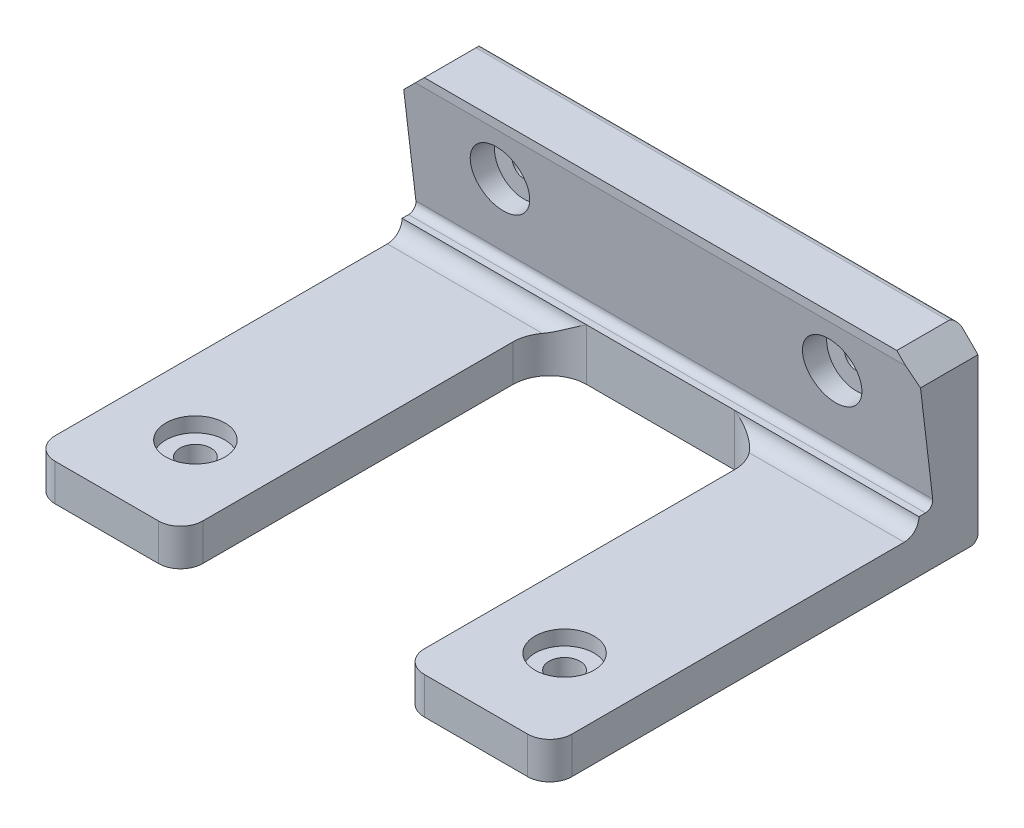
SolidWorks part; units mm, degrees
ref_plane "Přední rovina" through (0, 0, 0) normal (0, 0, 1) x (1, 0, 0)
ref_plane "Horní rovina" through (0, 0, 0) normal (0, 1, 0) x (1, 0, 0)
ref_plane "Pravá rovina" through (0, 0, 0) normal (1, 0, 0) x (0, 0, -1)
sketch "Sketch1" plane through (0, 0, 0) normal (0, 0, 1) x (1, 0, 0)
  line L1 (-35, 12.5) -> (35, 12.5)
  line L2 (-35, 12.5) -> (-35, -12.5)
  line L3 (-35, -12.5) -> (35, -12.5)
  line L4 (35, 12.5) -> (35, -12.5)
  line L5 (-35, 12.5) -> (35, -12.5) construction
  line L6 (-35, -12.5) -> (35, 12.5) construction
  point P0 (0, 0)
  dimension "D1" = 25
  dimension "D2" = 70
extrude "Boss-Extrude1" add sketch "Sketch1" along normal blind 8
sketch "Sketch2" plane through (0, 0, 8) normal (0, 0, 1) x (1, 0, 0)
  line L1 (-2.9445, -5.1) -> (2.9445, -5.1)
  line L2 (2.9445, -5.1) -> (5.889, 0)
  line L3 (5.889, 0) -> (2.9445, 5.1)
  line L4 (2.9445, 5.1) -> (-2.9445, 5.1)
  line L5 (-2.9445, 5.1) -> (-5.889, 0)
  line L6 (-5.889, 0) -> (-2.9445, -5.1)
  circle A0 centre (0, 0) radius 5.1 construction
  dimension "D1" = 10.2
extrude "Cut-Extrude1" [suppressed] cut sketch "Sketch2" against normal offset from surface (7 mm away) 1
sketch "Sketch3" [suppressed] plane through (0, 0, 1) normal (0, 0, 1) x (1, 0, 0)
  circle A0 centre (0, 0) radius 2.75
  dimension "D1" = 5.5
extrude "Cut-Extrude2" [suppressed] cut sketch "Sketch3" against normal through all
sketch "Sketch4" plane through (0, 0, 8) normal (0, 0, 1) x (1, 0, 0)
  line L1 (-35, -12.5) -> (-15, -12.5)
  line L2 (-35, -12.5) -> (-35, -7.5)
  line L3 (-35, -7.5) -> (-15, -7.5)
  line L4 (-15, -12.5) -> (-15, -7.5)
  dimension "D1" = 5
  dimension "D2" = 20
extrude "Boss-Extrude2" add sketch "Sketch4" along normal blind 50
sketch "Sketch5" plane through (-35, 0, 0) normal (-1, 0, 0) x (0, 0, 1)
  line L0 (58, -12.5) -> (61.6, -12.5)
  line L1 (61.6, -12.5) -> (61.6, 7.7)
  line L3 (58, -7.5) -> (58, 4.7)
  line L4 (58, -7.5) -> (8, -7.5) construction
  line L5 (58, 4.7) -> (55, 4.7)
  line L6 (55, 4.7) -> (55, 7.7)
  line L7 (55, 7.7) -> (61.6, 7.7)
  line L8 (58, -7.5) -> (58, -12.5)
  dimension "D1" = 3
  dimension "D2" = 3
  dimension "D3" = 3.6
  dimension "D4" = 12.2
extrude "Boss-Extrude3" [suppressed] add sketch "Sketch5" against normal up to surface (20 mm away)
ref_plane "Plane1" through (0, 0, 0) normal (-1, 0, 0) x (0, 0, 1)
mirror "Mirror1" about plane through (0, 0, 0) normal (-1, 0, 0) of "Boss-Extrude2", "Boss-Extrude3"
fillet "Fillet3" [suppressed] radius 2
fillet "Fillet1" [suppressed] radius 2
fillet "Fillet5" [suppressed] radius 1
sketch "Sketch7" [suppressed] plane through (35, 0, 0) normal (1, 0, 0) x (0, 0, -1)
  line L0 (-8, -5) -> (-8, 7.2)
  line L1 (-8, -7) -> (-8, 12) construction
  line L2 (-8, 7.2) -> (-7, 7.2)
  line L3 (-7, 7.2) -> (-6.5, -5)
  line L4 (-6.5, -5) -> (-8, -5)
  dimension "D1" = 2
  dimension "D2" = 12.2
  dimension "D3" = 1
  dimension "D4" = 1.5
extrude "Cut-Extrude3" [suppressed] cut sketch "Sketch7" against normal through all
fillet "Fillet6" [suppressed] radius 2
fillet "Fillet7" [suppressed] radius 5
fillet "Fillet8" [suppressed] radius 3
fillet "Fillet9" [suppressed] radius 1
fillet "Fillet10" [suppressed] radius 0.6
chamfer "Chamfer1" distance 3 angle 45 2 edges at (-35, 12.5, 4) (35, 12.5, 4)
sketch "Sketch10" plane through (-35, 0, 0) normal (-1, 0, 0) x (0, 0, 1)
  line L0 (8, 11.3) -> (6, -5.5)
  line L1 (8, 12.5) -> (8, 9.5) construction
  line L2 (6, -5.5) -> (8, -5.5)
  line L3 (8, 9.5) -> (8, -7.5) construction
  line L4 (8, -5.5) -> (8, 11.3)
  line L5 (58, -7.5) -> (8, -7.5) construction
  line L6 (0, 12.5) -> (8, 12.5) construction
  dimension "D1" = 2
  dimension "D2" = 2
  dimension "D3" = 1.2
  dimension "D4" = 16.8
extrude "Cut-Extrude5" cut sketch "Sketch10" against normal through all
fillet "Fillet13" radius 5 2 edges at (-15, -10, 8) (15, -10, 8)
fillet "Fillet14" radius 2 2 edges at (22.5, -7.5, 8) (-22.5, -7.5, 8)
fillet "Fillet15" radius 1 2 edges at (0, 12.5, 0) (0, -12.5, 0)
sketch "Sketch11" plane through (0, -7.5, 0) normal (0, 1, 0) x (1, 0, 0)
  line L0 (0, 0) -> (0, -52.7963) construction
  line L1 (-25, -58) -> (-25, -33.5997) construction
  line L3 (-15, -58) -> (-35, -58) construction
  circle A0 centre (-25, -46) radius 2.1
  circle A1 centre (25, -46) radius 2.1
  dimension "D2" = 4.2
  dimension "D1" = 12
extrude "Cut-Extrude6" cut sketch "Sketch11" against normal blind 10
fillet "Fillet18" radius 3 4 edges at (-15, -10, 58) (-35, -10, 58) (15, -10, 58) (35, -10, 58)
fillet "Fillet20" radius 1 1 edges at (0, -5.5, 6)
sketch "Sketch12" plane through (0, -0.7812, 6.5618) normal (0, -0.1182, 0.993) x (1, 0, 0)
  line L0 (0, 0) -> (0, 5) construction
  line L1 (-20, 5) -> (20, 5) construction
  dimension "D1" = 5
  dimension "D2" = 40
ref_plane "Plane2" through (0, 0, 8) normal (0, 0, -1) x (-1, 0, 0)
sketch "Sketch16" plane through (0, 0, 8) normal (0, 0, -1) x (-1, 0, 0)
  line L0 (-22.5, 5) -> (22.5, 5) construction
  line L1 (0, 5) -> (0, 0) construction
  circle A0 centre (-22.5, 5) radius 1.6
  circle A1 centre (22.5, 5) radius 1.6
  dimension "D2" = 3.2
  dimension "D1" = 45
  dimension "D3" = 5
extrude "Cut-Extrude11" cut sketch "Sketch16" along normal blind 10
sketch "Sketch17" plane through (0, 0, 8) normal (0, 0, -1) x (-1, 0, 0)
  circle A0 centre (-22.5, 5) radius 4
  circle A1 centre (22.5, 5) radius 4
  dimension "D1" = 8
extrude "Cut-Extrude12" cut sketch "Sketch17" along normal blind 4
sketch "Sketch18" plane through (0, -7.5, 0) normal (0, 1, 0) x (1, 0, 0)
  circle A0 centre (-25, -46) radius 4
  circle A1 centre (25, -46) radius 4
  dimension "D1" = 8
extrude "Cut-Extrude13" cut sketch "Sketch18" against normal blind 2
